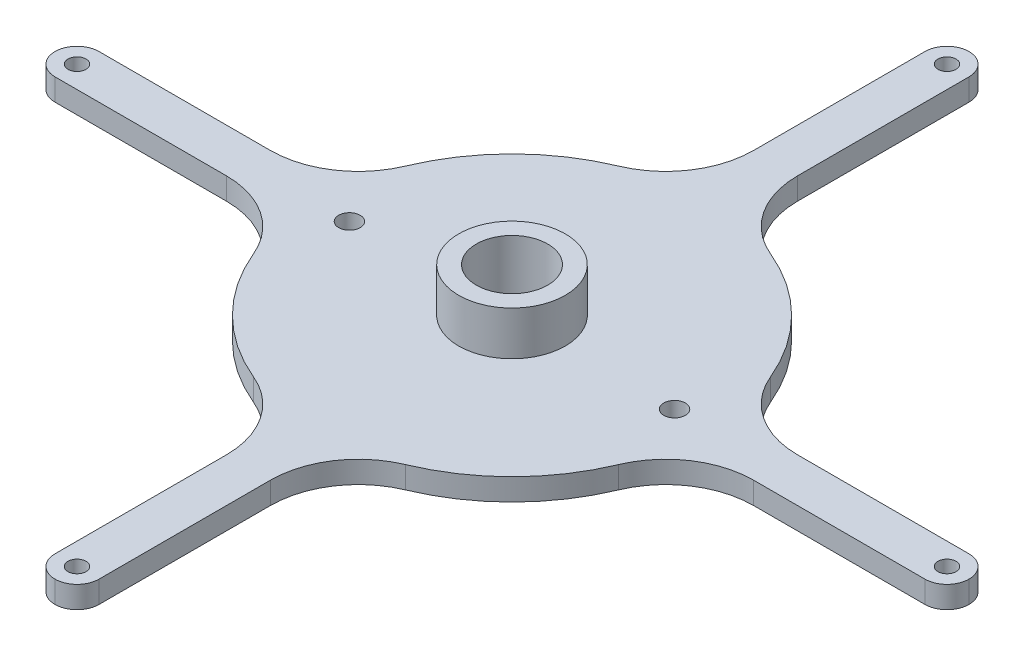
SolidWorks part; units mm, degrees
ref_plane "Alzado" through (0, 0, 0) normal (0, 0, 1) x (1, 0, 0)
ref_plane "Planta" through (0, 0, 0) normal (0, 1, 0) x (1, 0, 0)
ref_plane "Vista lateral" through (0, 0, 0) normal (1, 0, 0) x (0, 0, -1)
sketch "Croquis1" plane through (0, 0, 0) normal (0, 1, 0) x (1, 0, 0)
  line L0 (0, 0) -> (45, 0) construction
  line L1 (0, 45) -> (0, 0) construction
  circle A0 centre (0, 0) radius 45
  circle A1 centre (37, 0) radius 2.45
  circle A2 centre (0, 0) radius 37 construction
  circle A3 centre (-37, 0) radius 2.45
  circle A4 centre (0, 0) radius 8.125
  dimension "D1" = 90
  dimension "D2" = 4.9
  dimension "D3" = 8
  dimension "D4" = 16.25
extrude "Saliente-Extruir1" add sketch "Croquis1" along normal blind 5
extrude "Extruir-Lámina1" add sketch "Croquis1<2>" along normal blind 15 thin contours A4 thin type one direction wall 4
sketch "Croquis1<2>" plane through (0, 0, 0) normal (0, 1, 0) x (1, 0, 0) same geometry as "Croquis1"
ref_plane "Plano1" through (-12.125, 0, 0) normal (-1, 0, 0) x (0, 0, 1)
sketch "Croquis2" plane through (-12.125, 0, -11.125) normal (1, 0, 0) x (0, 0, -1)
  line L0 (1, 5) -> (1, 15) construction
  line L1 (1, 5) -> (1, 15) construction
  circle A0 centre (-11.125, 10) radius 2.425
  point P4 (1, 10)
  point P6 (0, 0)
  dimension "D1" = 4.85
extrude "Cortar-Extruir2" cut sketch "Croquis2" along normal blind 3
sketch "Croquis3" plane through (0, 0, 0) normal (0, 1, 0) x (1, 0, 0)
  line L0 (44.7214, 5) -> (104, 5)
  line L1 (-5, 44.7214) -> (5, 44.7214)
  line L2 (-5, 44.7214) -> (-5, 104)
  line L3 (-5, 104) -> (5, 104)
  line L4 (5, 44.7214) -> (5, 104)
  line L5 (44.7214, 5) -> (44.7214, -5)
  line L6 (44.7214, -5) -> (104, -5)
  line L7 (104, 5) -> (104, -5)
  line L8 (5, -44.7214) -> (5, -104)
  line L9 (5, -44.7214) -> (-5, -44.7214)
  line L10 (-5, -44.7214) -> (-5, -104)
  line L11 (5, -104) -> (-5, -104)
  line L12 (-44.7214, -5) -> (-104, -5)
  line L13 (-44.7214, -5) -> (-44.7214, 5)
  line L14 (-44.7214, 5) -> (-104, 5)
  line L15 (-104, -5) -> (-104, 5)
  circle A0 centre (0, 0) radius 45 construction
  circle A1 centre (0, 99) radius 2.05
  circle A2 centre (99, 0) radius 2.05
  circle A3 centre (0, -99) radius 2.05
  circle A4 centre (-99, 0) radius 2.05
  point P6 (0, 0)
  point P7 (0, 44.7214)
  point P11 (0, -44.7214)
  point P12 (5, -105.202)
  point P31 (0, 0)
  point P32 (5, -40.1434)
  point P33 (5, -67.2217)
  point P34 (0, 0)
  point P35 (-5, -36.872)
  dimension "D2" = 4.1
  dimension "D1" = 10
  dimension "D3" = 5
  dimension "D5" = 198
  dimension "D4" = 4
extrude "Saliente-Extruir2" add sketch "Croquis3" along normal blind 5
fillet "Redondeo1" radius 5 8 edges at (5, 2.5, 104) (-5, 2.5, 104) (-104, 2.5, 5) (-104, 2.5, -5) (-5, 2.5, -104) (5, 2.5, -104) (104, 2.5, -5) (104, 2.5, 5)
fillet "Redondeo2" radius 20 8 edges at (-5, 2.5, -44.7214) (-44.7214, 2.5, -5) (-44.7214, 2.5, 5) (-5, 2.5, 44.7214) (5, 2.5, 44.7214) (44.7214, 2.5, 5) (44.7214, 2.5, -5) (5, 2.5, -44.7214)
